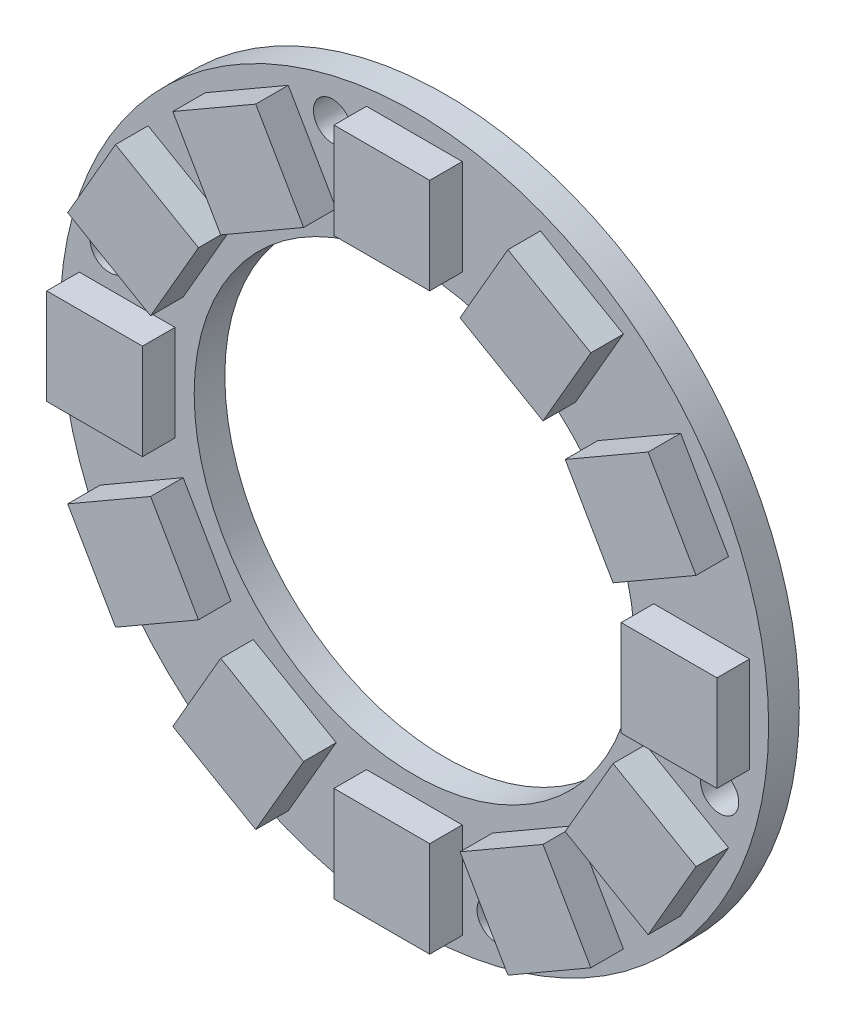
SolidWorks part; units mm, degrees
ref_plane "Front Plane" through (0, 0, 0) normal (0, 0, 1) x (1, 0, 0)
ref_plane "Top Plane" through (0, 0, 0) normal (0, 1, 0) x (1, 0, 0)
ref_plane "Right Plane" through (0, 0, 0) normal (1, 0, 0) x (0, 0, -1)
sketch "Sketch1" plane through (0, 0, 0) normal (0, 0, 1) x (1, 0, 0)
  circle A0 centre (0, 0) radius 11.5
  circle A1 centre (0, 0) radius 18.5
  dimension "D1" = 23
  dimension "D2" = 37
extrude "Boss-Extrude1" add sketch "Sketch1" along normal blind 1.6
sketch "Sketch2" plane through (0, 0, 1.6) normal (0, 0, 1) x (1, 0, 0)
  line L1 (-2.5, 17.5) -> (2.5, 17.5)
  line L2 (-2.5, 17.5) -> (-2.5, 12.5)
  line L3 (-2.5, 12.5) -> (2.5, 12.5)
  line L4 (2.5, 17.5) -> (2.5, 12.5)
  point P4 (0, 12.5)
  point P5 (-2.5, 15)
  dimension "D1" = 5
  dimension "D2" = 5
  dimension "D3" = 15
extrude "Boss-Extrude2" add sketch "Sketch2" along normal blind 1.7
ref_axis "Axis1" through (0, 0, 1.6) along (0, 0, -1)
pattern_circular "CirPattern1" count 12 over 360 about axis through (0, 0, 1.6) along (0, 0, -1) of "Boss-Extrude2"
sketch "Sketch3" plane through (0, 0, 1.6) normal (0, 0, 1) x (1, 0, 0)
  circle A0 centre (-4.2705, 15.9378) radius 1
  dimension "D1" = 16.5
  dimension "D2" = 2
  dimension "D3" = 2.3612
extrude "Cut-Extrude1" cut sketch "Sketch3" against normal blind 2
pattern_circular "CirPattern2" count 2 over 360 about axis through (0, 0, 1.6) along (0, 0, -1) of "Cut-Extrude1"
sketch "Sketch4" plane through (0, 0, 1.6) normal (0, 0, 1) x (1, 0, 0)
  circle A0 centre (-15.9378, 4.2705) radius 1
extrude "Cut-Extrude2" cut sketch "Sketch4" against normal blind 10
pattern_circular "CirPattern3" count 2 over 360 about axis through (0, 0, 1.6) along (0, 0, -1) of "Cut-Extrude2"
